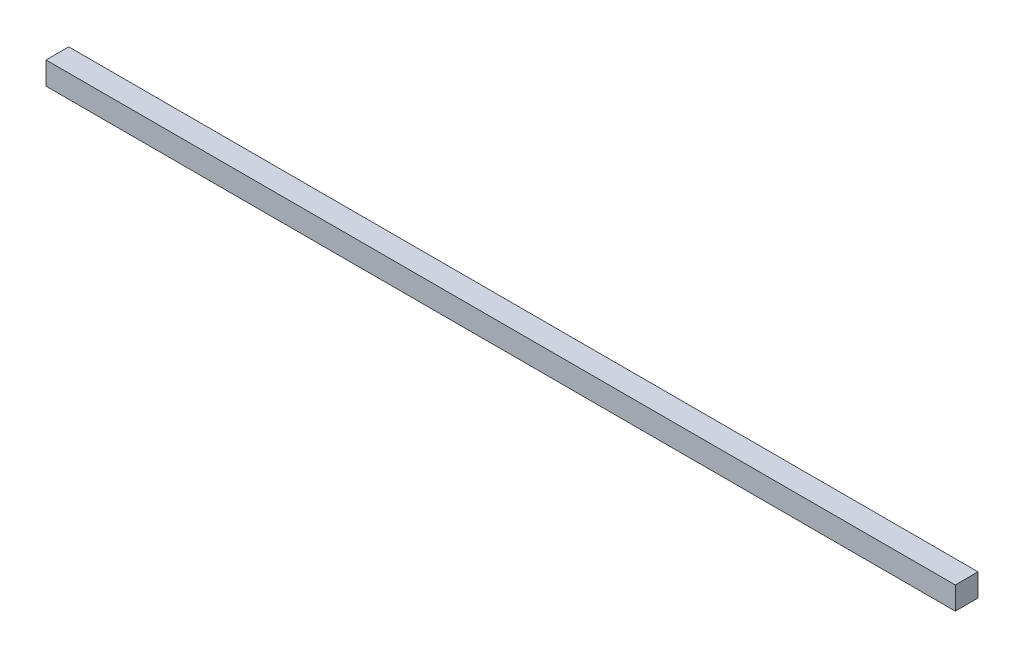
SolidWorks part; units mm, degrees
ref_plane "Front Plane" through (0, 0, 0) normal (0, 0, 1) x (1, 0, 0)
ref_plane "Top Plane" through (0, 0, 0) normal (0, 1, 0) x (1, 0, 0)
ref_plane "Right Plane" through (0, 0, 0) normal (1, 0, 0) x (0, 0, -1)
other "Configuration Table"
sketch "Sketch1" plane through (0, 0, 0) normal (0, 0, 1) x (1, 0, 0)
  line L1 (0, 0) -> (2032, 0)
  line L2 (0, 0) -> (0, 50.8)
  line L3 (0, 50.8) -> (2032, 50.8)
  line L4 (2032, 0) -> (2032, 50.8)
sheet metal parameters "Sheet-Metal1" thickness 50.8 parameters "D1"=0.7366
base flange "Base-Flange1" sketch "Sketch1" thickness 50.8 reverse thickness direction yes parameters "D1"=0.7366
flat pattern "Flat-Pattern1" [suppressed]
sketch "Bend-Lines1" plane through (0, 0, 0) normal (0, 1, 0) x (-1, 0, 0)
